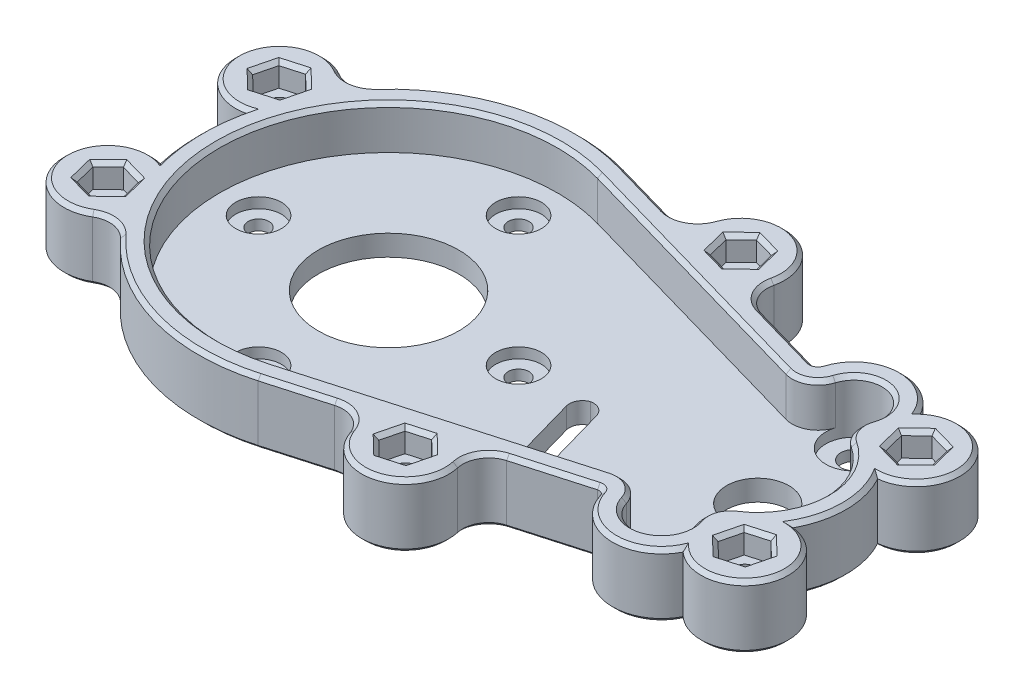
SolidWorks part; units mm, degrees
ref_plane "Front Plane" through (0, 0, 0) normal (0, 0, 1) x (1, 0, 0)
ref_plane "Top Plane" through (0, 0, 0) normal (0, 1, 0) x (1, 0, 0)
ref_plane "Right Plane" through (0, 0, 0) normal (1, 0, 0) x (0, 0, -1)
sketch "Sketch1" plane through (0, 0, 0) normal (0, 1, 0) x (1, 0, 0)
  line L0 (0, 73.0538) -> (0, -65.1274) construction
  line L1 (35.5, 6.365) -> (-28.5632, 24.502) construction
  line L2 (-70.6215, 0) -> (67.3742, 0) construction
  line L3 (35.5, -6.365) -> (-28.5632, -24.502) construction
  line L4 (4.5177, -15.1364) -> (0.1592, 0.2585)
  line L5 (0.1592, 0.2585) -> (4.6815, 1.5388)
  line L6 (4.6815, 1.5388) -> (9.04, -13.8561)
  line L7 (9.04, -13.8561) -> (9.5848, -15.7805)
  line L8 (9.5848, -15.7805) -> (5.0625, -17.0608)
  line L9 (5.0625, -17.0608) -> (4.5177, -15.1364)
  line L10 (-35.5, 0) -> (-60.5, 0) construction
  line L11 (-35.5, 0) -> (-35.5, 25) construction
  line L13 (-100, -75) -> (100, -75)
  line L14 (-100, -75) -> (-100, 75)
  line L15 (-100, 75) -> (100, 75)
  line L16 (100, -75) -> (100, 75)
  line L17 (-100, -75) -> (100, 75) construction
  line L18 (-100, 75) -> (100, -75) construction
  circle A0 centre (35.5, 0) radius 6
  circle A1 centre (-35.5, 0) radius 13.5
  circle A2 centre (-35.5, 0) radius 25.465 construction
  circle A3 centre (35.5, 0) radius 6.365 construction
  circle A4 centre (-60.5, 0) radius 2
  circle A5 centre (-35.5, 25) radius 2
  circle A6 centre (-10.5, 0) radius 2
  circle A7 centre (-35.5, -25) radius 2
  circle A8 centre (35.5, 18.5) radius 2.5
  circle A9 centre (35.5, -18.5) radius 2.5
  point P35 (0, 0)
  dimension "D1" = 12
  dimension "D2" = 27
  dimension "D5" = 50.93
  dimension "D6" = 12.73
  dimension "D12" = 4
  dimension "D19" = 5
  dimension "D3" = 71
  dimension "D4" = 35.5
  dimension "D7" = 90
  dimension "D8" = 27.5
  dimension "D9" = 4.7
  dimension "D10" = 16
  dimension "D11" = 2
  dimension "D13" = 25
  dimension "D15" = 90
  dimension "D16" = 25
  dimension "D17" = 200
  dimension "D18" = 150
  dimension "D20" = 18.5
  dimension "D14" = 4
extrude "Boss-Extrude1" add sketch "Sketch1" along normal blind 4
sketch "Sketch3" plane through (0, 4, 0) normal (0, 1, 0) x (1, 0, 0)
  line L0 (-26.5739, 31.2502) -> (39.0704, 12.5001)
  line L1 (-100, -75) -> (100, -75)
  line L2 (-100, -75) -> (-100, 75)
  line L3 (-100, 75) -> (100, 75)
  line L4 (100, -75) -> (100, 75)
  line L5 (-35.5, 0) -> (35.5, 0) construction
  line L6 (-26.5739, -31.2502) -> (39.0704, -12.5001)
  arc A0 (-26.5739, 31.2502) -> (-26.5739, -31.2502) centre (-35.5, 0) ccw
  arc A1 (39.0704, -12.5001) -> (39.0704, 12.5001) centre (35.5, 0) ccw
  dimension "D1" = 65
  dimension "D2" = 26
extrude "Boss-Extrude2" add sketch "Sketch3" along normal blind 8.25 contours L2 L1 L4 L3
sketch "Sketch6" plane through (0, 12.25, 0) normal (0, 1, 0) x (1, 0, 0)
  circle A0 centre (35.5, 18.5) radius 5.4
  circle A1 centre (35.5, -18.5) radius 5.4
  dimension "D1" = 10.8
extrude "Cut-Extrude2" cut sketch "Sketch6" against normal up to surface (8.25 mm away) up to face at (-35.5, 4, 27)
fillet "Fillet1" radius 2.5 4 edges at (9.5848, 2, 15.7805) (5.0625, 2, 17.0608) (4.6815, 2, -1.5388) (0.1592, 2, -0.2585)
fillet "Fillet2" radius 5 4 edges at (31.7849, 8.125, 14.5811) (36.5847, 8.125, 13.2101) (36.5847, 8.125, -13.2101) (31.7849, 8.125, -14.5811)
sketch "Sketch2" plane through (0, 4, 0) normal (0, 1, 0) x (1, 0, 0)
  line L0 (29.5, 0) -> (41.5, 0) construction
  line L1 (35.5, 0) -> (35.5, -6) construction
  line L2 (35.5, 0) -> (35.5, 6) construction
  circle A0 centre (-35.5, 25) radius 4.4
  circle A1 centre (-10.5, 0) radius 4.4
  circle A2 centre (-35.5, -25) radius 4.4
  circle A3 centre (-60.5, 0) radius 4.4
  circle A4 centre (35.5, 0) radius 6 construction
  circle A7 centre (35.5, 18.5) radius 5.4
  circle A8 centre (35.5, -18.5) radius 5.4
  arc A9 (40.6003, 16.7261) -> (30.3389, 20.0883) centre (35.5, 18.5) ccw construction
  dimension "D1" = 8.8
extrude "Cut-Extrude1" cut sketch "Sketch2" against normal blind 2
sketch "Sketch8" plane through (0, 0, 0) normal (0, -1, 0) x (1, 0, 0)
  line L0 (-35.5, 0) -> (-100, 0) construction
  line L1 (-100, -75) -> (-100, 75) construction
  line L2 (-35.5, 0) -> (100, 0) construction
  line L3 (100, 75) -> (100, -75) construction
  line L4 (49.5, 21.4955) -> (49.5, -20.5045) construction
  line L5 (0, 32.8542) -> (0, -34.16) construction
  line L6 (-73, 27.0496) -> (-73, -26.9504) construction
  line L11 (-26.5739, -31.2502) -> (24.1868, -16.7513)
  line L12 (24.1868, 16.7513) -> (-26.5739, 31.2502)
  line L13 (-26.5739, -31.2502) -> (24.1868, -16.7513) construction
  line L14 (24.1868, 16.7513) -> (-26.5739, 31.2502) construction
  circle A0 centre (-35.5, 0) radius 32.5 construction
  arc A1 (-26.5739, 31.2502) -> (-26.5739, -31.2502) centre (-35.5, 0) ccw construction
  circle A13 centre (49.5, 16.5) radius 2
  circle A14 centre (-73, 16.5) radius 2
  circle A15 centre (0, 32.25) radius 2
  circle A16 centre (49.5, 16.5) radius 4.4 construction
  circle A17 centre (0, 32.25) radius 4.4 construction
  circle A18 centre (-73, 16.5) radius 4.4 construction
  circle A19 centre (35.5, 18.5) radius 5.4 construction
  arc A20 (40.6003, 16.7261) -> (30.3389, 20.0883) centre (35.5, 18.5) ccw construction
  circle A21 centre (35.5, -18.5) radius 5.4 construction
  circle A22 centre (-73, -16.5) radius 4.4 construction
  circle A23 centre (-73, -16.5) radius 2
  circle A24 centre (0, -32.25) radius 4.4 construction
  circle A25 centre (0, -32.25) radius 2
  circle A26 centre (49.5, -16.5) radius 4.4 construction
  circle A27 centre (49.5, -16.5) radius 2
  circle A28 centre (49.5, 16.5) radius 8.4 construction
  circle A29 centre (0, 32.25) radius 8.4 construction
  circle A30 centre (-73, 16.5) radius 8.4 construction
  arc A44 (30.3389, -20.0883) -> (40.6003, -16.7261) centre (35.5, -18.5) ccw
  arc A45 (42.5943, -10.8936) -> (40.6003, -16.7261) centre (45.3228, -15.0835) ccw
  arc A46 (42.5943, -10.8936) -> (42.5943, 10.8936) centre (35.5, 0) ccw
  arc A47 (40.6003, 16.7261) -> (42.5943, 10.8936) centre (45.3228, 15.0835) ccw
  arc A48 (30.3389, -20.0883) -> (24.1868, -16.7513) centre (25.5601, -21.559) ccw
  arc A49 (40.6003, 16.7261) -> (30.3389, 20.0883) centre (35.5, 18.5) ccw
  arc A50 (24.1868, 16.7513) -> (30.3389, 20.0883) centre (25.5601, 21.559) ccw
  arc A51 (-26.5739, 31.2502) -> (-26.5739, -31.2502) centre (-35.5, 0) ccw
  arc A52 (30.3389, -20.0883) -> (40.6003, -16.7261) centre (35.5, -18.5) ccw construction
  arc A53 (42.5943, -10.8936) -> (40.6003, -16.7261) centre (45.3228, -15.0835) ccw construction
  arc A54 (42.5943, -10.8936) -> (42.5943, 10.8936) centre (35.5, 0) ccw construction
  arc A55 (40.6003, 16.7261) -> (42.5943, 10.8936) centre (45.3228, 15.0835) ccw construction
  arc A56 (30.3389, -20.0883) -> (24.1868, -16.7513) centre (25.5601, -21.559) ccw construction
  arc A57 (40.6003, 16.7261) -> (30.3389, 20.0883) centre (35.5, 18.5) ccw construction
  arc A58 (24.1868, 16.7513) -> (30.3389, 20.0883) centre (25.5601, 21.559) ccw construction
  arc A59 (-26.5739, 31.2502) -> (-26.5739, -31.2502) centre (-35.5, 0) ccw construction
  dimension "D1" = 0
  dimension "D2" = 4
  dimension "D4" = 33
  dimension "D5" = 49.5
  dimension "D3" = 8.8
  dimension "D8" = 16.8
  dimension "D6" = 64.5
  dimension "D7" = 73
extrude "Cut-Extrude3" cut sketch "Sketch8" against normal through all both and the other way through all
sketch "Sketch13" plane through (0, 12.25, 0) normal (0, 1, 0) x (1, 0, 0)
  line L0 (-100, 0) -> (100, 0) construction
  line L1 (-100, 75) -> (-100, -75) construction
  line L2 (100, -75) -> (100, 75) construction
  line L5 (-8.1313, 30.1424) -> (-25.4754, 35.0964)
  line L6 (5.7914, -26.1656) -> (25.2854, -20.5975)
  line L7 (-25.4754, -35.0964) -> (25.2854, -20.5975)
  line L8 (25.2854, 20.5975) -> (-25.4754, 35.0964)
  line L9 (-25.4754, -35.0964) -> (-8.1313, -30.1424)
  line L10 (25.2854, 20.5975) -> (5.7914, 26.1656)
  arc A0 (5.7914, 26.1656) -> (-8.1313, 30.1424) centre (0, 32.25) ccw
  arc A1 (50.4188, 8.1504) -> (43.8854, 22.7479) centre (49.5, 16.5) ccw
  arc A2 (-65.6518, 20.5699) -> (-71.0361, 8.3328) centre (-73, 16.5) ccw
  arc A3 (-65.6518, -20.5699) -> (-71.0361, -8.3328) centre (-73, -16.5) cw
  arc A4 (5.7914, -26.1656) -> (-8.1313, -30.1424) centre (0, -32.25) cw
  arc A5 (50.4188, -8.1504) -> (43.8854, -22.7479) centre (49.5, -16.5) cw
  arc A14 (-71.0361, 8.3328) -> (-71.0361, -8.3328) centre (-35.5, 0) ccw
  arc A15 (-65.6518, -20.5699) -> (-25.4754, -35.0964) centre (-35.5, 0) ccw
  arc A22 (44.3783, 15.412) -> (26.5158, 21.2649) centre (35.5, 18.5) ccw
  arc A23 (44.3783, 15.412) -> (44.7771, 14.2455) centre (45.3228, 15.0835) ccw
  arc A24 (44.7771, -14.2455) -> (44.7771, 14.2455) centre (35.5, 0) ccw
  arc A25 (44.7771, -14.2455) -> (44.3783, -15.412) centre (45.3228, -15.0835) ccw
  arc A26 (26.5158, -21.2649) -> (44.3783, -15.412) centre (35.5, -18.5) ccw
  arc A27 (26.5158, -21.2649) -> (25.2854, -20.5975) centre (25.5601, -21.559) ccw
  arc A28 (-25.4754, 35.0964) -> (-25.4754, -35.0964) centre (-35.5, 0) ccw
  arc A29 (25.2854, 20.5975) -> (26.5158, 21.2649) centre (25.5601, 21.559) ccw
  arc A30 (43.8854, 22.7479) -> (26.5158, 21.2649) centre (35.5, 18.5) ccw
  arc A32 (50.4188, -8.1504) -> (50.4188, 8.1504) centre (35.5, 0) ccw
  arc A34 (26.5158, -21.2649) -> (43.8854, -22.7479) centre (35.5, -18.5) ccw
  arc A35 (26.5158, -21.2649) -> (25.2854, -20.5975) centre (25.5601, -21.559) ccw
  arc A36 (-25.4754, 35.0964) -> (-65.6518, 20.5699) centre (-35.5, 0) ccw
  arc A37 (25.2854, 20.5975) -> (26.5158, 21.2649) centre (25.5601, 21.559) ccw
  dimension "D1" = 16.8
  dimension "D2" = 4
extrude "Cut-Extrude6" cut sketch "Sketch13" against normal through all both and the other way through all flip side to cut
fillet "Fillet4" radius 5 6 edges at (-65.6518, 6.125, 20.5699) (-65.6518, 6.125, -20.5699) (-8.1313, 6.125, -30.1424) (5.7914, 6.125, -26.1656) (5.7914, 6.125, 26.1656) (-8.1313, 6.125, 30.1424)
sketch "Sketch14" plane through (0, 12.25, 0) normal (0, 1, 0) x (1, 0, 0)
  line L0 (24.1868, 16.7513) -> (-26.5739, 31.2502) construction
  line L1 (2.9873, 35.1407) -> (-1.0098, 36.2824)
  line L2 (-1.0098, 36.2824) -> (-3.9971, 33.3917)
  line L3 (-3.9971, 33.3917) -> (-2.9873, 29.3593)
  line L4 (-2.9873, 29.3593) -> (1.0098, 28.2176)
  line L5 (1.0098, 28.2176) -> (3.9971, 31.1083)
  line L6 (3.9971, 31.1083) -> (2.9873, 35.1407)
  line L7 (-26.5739, -31.2502) -> (24.1868, -16.7513) construction
  line L8 (-2.9873, -29.3593) -> (-3.9971, -33.3917)
  line L9 (-3.9971, -33.3917) -> (-1.0098, -36.2824)
  line L10 (-1.0098, -36.2824) -> (2.9873, -35.1407)
  line L11 (2.9873, -35.1407) -> (3.9971, -31.1083)
  line L12 (3.9971, -31.1083) -> (1.0098, -28.2176)
  line L13 (1.0098, -28.2176) -> (-2.9873, -29.3593)
  line L15 (52.4873, 19.3907) -> (48.4902, 20.5324)
  line L16 (48.4902, 20.5324) -> (45.5029, 17.6417)
  line L17 (45.5029, 17.6417) -> (46.5127, 13.6093)
  line L18 (46.5127, 13.6093) -> (50.5098, 12.4676)
  line L19 (50.5098, 12.4676) -> (53.4971, 15.3583)
  line L20 (53.4971, 15.3583) -> (52.4873, 19.3907)
  line L23 (53.4971, -15.3583) -> (50.5098, -12.4676)
  line L24 (50.5098, -12.4676) -> (46.5127, -13.6093)
  line L25 (46.5127, -13.6093) -> (45.5029, -17.6417)
  line L26 (45.5029, -17.6417) -> (48.4902, -20.5324)
  line L27 (48.4902, -20.5324) -> (52.4873, -19.3907)
  line L28 (52.4873, -19.3907) -> (53.4971, -15.3583)
  line L29 (-69.0029, 17.6417) -> (-71.9902, 20.5324)
  line L30 (-71.9902, 20.5324) -> (-75.9873, 19.3907)
  line L31 (-75.9873, 19.3907) -> (-76.9971, 15.3583)
  line L32 (-76.9971, 15.3583) -> (-74.0098, 12.4676)
  line L33 (-74.0098, 12.4676) -> (-70.0127, 13.6093)
  line L34 (-70.0127, 13.6093) -> (-69.0029, 17.6417)
  line L35 (-70.0127, -13.6093) -> (-74.0098, -12.4676)
  line L36 (-74.0098, -12.4676) -> (-76.9971, -15.3583)
  line L37 (-76.9971, -15.3583) -> (-75.9873, -19.3907)
  line L38 (-75.9873, -19.3907) -> (-71.9902, -20.5324)
  line L39 (-71.9902, -20.5324) -> (-69.0029, -17.6417)
  line L40 (-69.0029, -17.6417) -> (-70.0127, -13.6093)
  circle A0 centre (0, 32.25) radius 3.6 construction
  circle A1 centre (0, -32.25) radius 3.6 construction
  circle A2 centre (49.5, 16.5) radius 3.6 construction
  circle A4 centre (49.5, -16.5) radius 3.6 construction
  circle A5 centre (-73, 16.5) radius 3.6 construction
  circle A6 centre (-73, -16.5) radius 3.6 construction
  point P41 (-75.5034, 13.913)
  dimension "D1" = 7.2
  dimension "D2" = 7.2
  dimension "D3" = 7.2
  dimension "D4" = 7.2
  dimension "D5" = 7.2
  dimension "D6" = 7.2
extrude "Cut-Extrude7" cut sketch "Sketch14" against normal blind 4.5
chamfer "Chamfer1" distance 0.75 angle 45 94 edges at (-81.3041, 12.25, -17.7658) (-65.4012, 12.25, -23.0566) (-45.4449, 12.25, -35.1191) (-19.7552, 12.25, -33.4625) (-10.3549, 12.25, -32.2003) (2.307, 12.25, -40.327) (8.7665, 12.25, -26.7387) (18.4902, 12.25, -22.5384) (26.0369, 12.25, -20.68) (34.7003, 12.25, -27.8659) (57.1671, 12.25, -19.9316) (52.5, 12.25, 0) (57.1671, 12.25, 19.9316) (34.7003, 12.25, 27.8659) (26.0369, 12.25, 20.68) (18.4902, 12.25, 22.5384) (8.7665, 12.25, 26.7387) (2.307, 12.25, 40.327) (-10.3549, 12.25, 32.2003) (-19.7552, 12.25, 33.4625) (-45.4449, 12.25, 35.1191) (-65.4012, 12.25, 23.0566) (-81.3041, 12.25, 17.7658) (-72, 12.25, 0) (40.5917, 12.25, -13.4661) (37.1814, 12.25, -23.6316) (27.9441, 12.25, -17.164) (-1.1936, 12.25, -24.0008) (-68, 12.25, 0) (-1.1936, 12.25, 24.0008) (27.9441, 12.25, 17.164) (37.1814, 12.25, 23.6316) (40.5917, 12.25, 13.4661) (48.5, 12.25, 0) (-73.9887, 12.25, -19.9616) (-76.4922, 12.25, -17.3745) (-75.5034, 12.25, -13.913) (-72.0113, 12.25, -13.0384) (-69.5078, 12.25, -15.6255) (-70.4966, 12.25, -19.087) (48.5113, 12.25, 13.0384) (46.0078, 12.25, 15.6255) (46.9966, 12.25, 19.087) (50.4887, 12.25, 19.9616) (52.9922, 12.25, 17.3745) (52.0034, 12.25, 13.913) (-2.5034, 12.25, 34.837) (0.9887, 12.25, 35.7116) (3.4922, 12.25, 33.1245) (2.5034, 12.25, 29.663) (-0.9887, 12.25, 28.7884) (-3.4922, 12.25, 31.3755) (46.9966, 12.25, -19.087) (46.0078, 12.25, -15.6255) (48.5113, 12.25, -13.0384) (52.0034, 12.25, -13.913) (52.9922, 12.25, -17.3745) (50.4887, 12.25, -19.9616) (-75.5034, 12.25, 13.913) (-76.4922, 12.25, 17.3745) (-73.9887, 12.25, 19.9616) (-70.4966, 12.25, 19.087) (-69.5078, 12.25, 15.6255) (-72.0113, 12.25, 13.0384) (-2.5034, 12.25, -34.837) (-3.4922, 12.25, -31.3755) (-0.9887, 12.25, -28.7884) (2.5034, 12.25, -29.663) (3.4922, 12.25, -33.1245) (0.9887, 12.25, -35.7116) (-19.7552, 0, -33.4625) (-45.4449, 0, -35.1191) (-65.4012, 0, -23.0566) (-81.3041, 0, -17.7658) (-72, 0, 0) (-81.3041, 0, 17.7658) (-65.4012, 0, 23.0566) (-10.3549, 0, -32.2003) (2.307, 0, -40.327) (8.7665, 0, -26.7387) (18.4902, 0, -22.5384) (26.0369, 0, -20.68) (-45.4449, 0, 35.1191) (-19.7552, 0, 33.4625) (-10.3549, 0, 32.2003) (2.307, 0, 40.327) (8.7665, 0, 26.7387) (18.4902, 0, 22.5384) (26.0369, 0, 20.68) (34.7003, 0, -27.8659) (34.7003, 0, 27.8659) (57.1671, 0, -19.9316) (52.5, 0, 0) (57.1671, 0, 19.9316)
